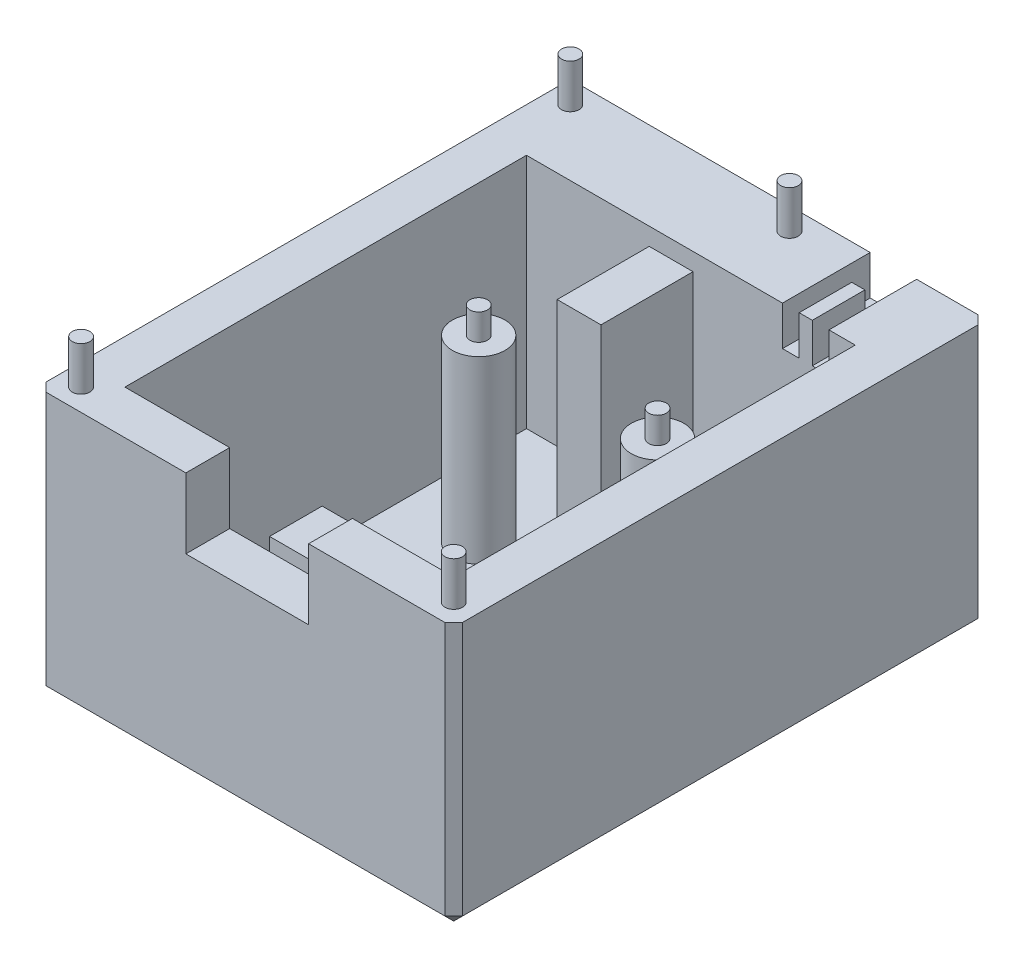
SolidWorks part; units mm, degrees
ref_plane "前视基准面" through (0, 0, 0) normal (0, 0, 1) x (1, 0, 0)
ref_plane "上视基准面" through (0, 0, 0) normal (0, 1, 0) x (1, 0, 0)
ref_plane "右视基准面" through (0, 0, 0) normal (1, 0, 0) x (0, 0, -1)
other "Configuration Table"
sketch "草图1" plane through (0, 0, 0) normal (0, 1, 0) x (1, 0, 0)
  line L1 (-50.0333, 28.8167) -> (-2.5333, 28.8167)
  line L2 (-50.0333, 28.8167) -> (-50.0333, -31.9833)
  line L3 (-50.0333, -31.9833) -> (-2.5333, -31.9833)
  line L4 (-2.5333, 28.8167) -> (-2.5333, -31.9833)
  dimension "D1" = 47.5
  dimension "D2" = 60.8
extrude "凸台-拉伸1" add sketch "草图1" along normal blind 30
sketch "草图2" plane through (0, 30, 0) normal (0, 1, 0) x (1, 0, 0)
  line L0 (-2.5333, -31.9833) -> (-2.5333, 28.8167) construction
  line L1 (-2.5333, 28.8167) -> (-50.0333, 28.8167) construction
  line L2 (-50.0333, 28.8167) -> (-50.0333, -31.9833) construction
  line L3 (-50.0333, -31.9833) -> (-2.5333, -31.9833) construction
  circle A0 centre (-22.5333, 26.3167) radius 1
  circle A1 centre (-47.5333, 26.3167) radius 1
  circle A2 centre (-47.5333, -29.4833) radius 1
  circle A3 centre (-5.0333, -29.4833) radius 1
  dimension "D1" = 20
  dimension "D3" = 2.5
  dimension "D5" = 2.5
  dimension "D7" = 2.5
  dimension "D2" = 2.5
  dimension "D4" = 2.5
  dimension "D6" = 2.5
  dimension "D8" = 2.5
extrude "凸台-拉伸3" add sketch "草图2" along normal blind 5
sketch "草图3" plane through (0, 30, 0) normal (0, 1, 0) x (1, 0, 0)
  line L0 (-50.0333, 28.8167) -> (-50.0333, -31.9833) construction
  line L1 (-45.0333, 18.8167) -> (-7.5333, 18.8167)
  line L2 (-45.0333, 18.8167) -> (-45.0333, -26.9833)
  line L3 (-45.0333, -26.9833) -> (-7.5333, -26.9833)
  line L4 (-7.5333, 18.8167) -> (-7.5333, -26.9833)
  line L5 (-2.5333, -31.9833) -> (-2.5333, 28.8167) construction
  line L6 (-2.5333, 28.8167) -> (-50.0333, 28.8167) construction
  line L7 (-50.0333, -31.9833) -> (-2.5333, -31.9833) construction
  dimension "D1" = 5
  dimension "D2" = 5
  dimension "D3" = 10
  dimension "D4" = 5
extrude "切除-拉伸1" cut sketch "草图3" against normal blind 27
sketch "草图4" plane through (0, 30, 0) normal (0, 1, 0) x (1, 0, 0)
  line L0 (-45.0333, -26.9833) -> (-7.5333, -26.9833) construction
  line L1 (-33.0833, -26.9833) -> (-19.0833, -26.9833)
  line L2 (-33.0833, -26.9833) -> (-33.0833, -31.9833)
  line L3 (-33.0833, -31.9833) -> (-19.0833, -31.9833)
  line L4 (-19.0833, -26.9833) -> (-19.0833, -31.9833)
  line L5 (-50.0333, -31.9833) -> (-2.5333, -31.9833) construction
  line L6 (-2.5333, -31.9833) -> (-2.5333, 28.8167) construction
  dimension "D1" = 16.55
  dimension "D2" = 14
extrude "切除-拉伸2" cut sketch "草图4" against normal blind 8
sketch "草图5" plane through (0, 3, 0) normal (0, 1, 0) x (1, 0, 0)
  line L0 (-2.5333, -31.9833) -> (-2.5333, 28.8167) construction
  line L2 (-2.5333, 28.8167) -> (-50.0333, 28.8167) construction
  line L3 (-50.0333, 28.8167) -> (-50.0333, -31.9833) construction
  line L4 (-45.0333, -26.9833) -> (-7.5333, -26.9833) construction
  line L5 (-28.5333, -20.9833) -> (-22.5333, -20.9833)
  line L6 (-28.5333, -20.9833) -> (-28.5333, -26.9833)
  line L7 (-28.5333, -26.9833) -> (-22.5333, -26.9833)
  line L8 (-22.5333, -20.9833) -> (-22.5333, -26.9833)
  line L9 (-7.5333, -26.9833) -> (-7.5333, 18.8167) construction
  circle A0 centre (-16.0833, 4.8167) radius 3
  circle A1 centre (-36.4833, 4.8167) radius 3
  point P16 (-25.5333, -20.9833)
  point P19 (-28.5333, -23.9833)
  dimension "D1" = 13.55
  dimension "D3" = 13.55
  dimension "D2" = 24
  dimension "D4" = 24
  dimension "D5" = 6
  dimension "D6" = 15
  dimension "D7" = 6
  dimension "D8" = 31.8
extrude "凸台-拉伸4" add sketch "草图5" along normal blind 20.5
sketch "草图6" plane through (0, 3, 0) normal (0, 1, 0) x (1, 0, 0)
  line L0 (-7.5333, 18.8167) -> (-45.0333, 18.8167) construction
  line L1 (-31.0333, 18.8167) -> (-26.0333, 18.8167)
  line L2 (-31.0333, 18.8167) -> (-31.0333, 8.3167)
  line L3 (-31.0333, 8.3167) -> (-26.0333, 8.3167)
  line L4 (-26.0333, 18.8167) -> (-26.0333, 8.3167)
  line L5 (-45.0333, 18.8167) -> (-45.0333, -26.9833) construction
  line L6 (-50.0333, 28.8167) -> (-50.0333, -31.9833) construction
  circle A1 centre (-36.4833, 4.8167) radius 3
  circle A2 centre (-36.4833, 4.8167) radius 3 construction
  dimension "D1" = 0
  dimension "D2" = 3.5
  dimension "D3" = 5
  dimension "D4" = 0
  dimension "D5" = 14
extrude "凸台-拉伸6" add sketch "草图6" along normal blind 25
sketch "草图7" plane through (0, 23.5, 0) normal (0, 1, 0) x (1, 0, 0)
  circle A0 centre (-36.4833, 4.8167) radius 1
  circle A1 centre (-16.0833, 4.8167) radius 1
extrude "凸台-拉伸7" add sketch "草图7" along normal blind 3
sketch "草图12" plane through (0, 0, -28.8167) normal (0, 0, -1) x (-1, 0, 0)
  line L0 (2.5333, 30) -> (50.0333, 30) construction
  line L1 (10.5333, 30) -> (15.8333, 30)
  line L2 (10.5333, 30) -> (10.5333, 25.5)
  line L3 (10.5333, 25.5) -> (15.8333, 25.5)
  line L4 (15.8333, 30) -> (15.8333, 25.5)
  line L5 (2.5333, 30) -> (2.5333, 0) construction
  dimension "D1" = 8
  dimension "D2" = 5.3
  dimension "D3" = 4.5
extrude "切除-拉伸5" cut sketch "草图12" against normal blind 10
sketch "草图13" plane through (0, 25.5, 0) normal (0, 1, 0) x (1, 0, 0)
  line L0 (-10.5333, 18.8167) -> (-15.8333, 18.8167) construction
  line L1 (-13.9333, 24.8167) -> (-12.4333, 24.8167)
  line L2 (-13.9333, 24.8167) -> (-13.9333, 18.8167)
  line L3 (-13.9333, 18.8167) -> (-12.4333, 18.8167)
  line L4 (-12.4333, 24.8167) -> (-12.4333, 18.8167)
  line L5 (-10.5333, 28.8167) -> (-15.8333, 28.8167) construction
  line L6 (-10.5333, 18.8167) -> (-10.5333, 28.8167) construction
  point P6 (-13.1833, 24.8167)
  dimension "D1" = 4
  dimension "D2" = 1.9
  dimension "D3" = 1.5
extrude "凸台-拉伸8" add sketch "草图13" along normal blind 4.5
sketch "草图14" plane through (0, 3, 0) normal (0, 1, 0) x (1, 0, 0)
  line L0 (-45.0333, 18.8167) -> (-45.0333, -26.9833) construction
  line L1 (-41.0333, -0.5904) -> (-11.0333, -0.5904)
  line L2 (-41.0333, -0.5904) -> (-41.0333, -3.5904)
  line L3 (-41.0333, -3.5904) -> (-11.0333, -3.5904)
  line L4 (-11.0333, -0.5904) -> (-11.0333, -3.5904)
  line L5 (-41.0333, -6.5904) -> (-41.0333, -9.5904)
  line L6 (-41.0333, -6.5904) -> (-11.0333, -6.5904)
  line L7 (-11.0333, -6.5904) -> (-11.0333, -9.5904)
  line L8 (-41.0333, -9.5904) -> (-11.0333, -9.5904)
  line L9 (-41.0333, -12.5904) -> (-41.0333, -15.5904)
  line L10 (-41.0333, -12.5904) -> (-11.0333, -12.5904)
  line L11 (-11.0333, -12.5904) -> (-11.0333, -15.5904)
  line L12 (-41.0333, -15.5904) -> (-11.0333, -15.5904)
  point P4 (-41.0333, -2.0904)
  dimension "D1" = 3
  dimension "D2" = 30
  dimension "D3" = 4
  dimension "D4" = 3
extrude "切除-拉伸6" cut sketch "草图14" against normal blind 3
chamfer "倒角1" distance 1 angle 45 8 edges at (-2.5333, 15, 31.9833) (-26.2833, 0, 31.9833) (-50.0333, 15, 31.9833) (-50.0333, 0, 1.5833) (-50.0333, 15, -28.8167) (-2.5333, 0, 1.5833) (-26.2833, 0, -28.8167) (-2.5333, 15, -28.8167)
